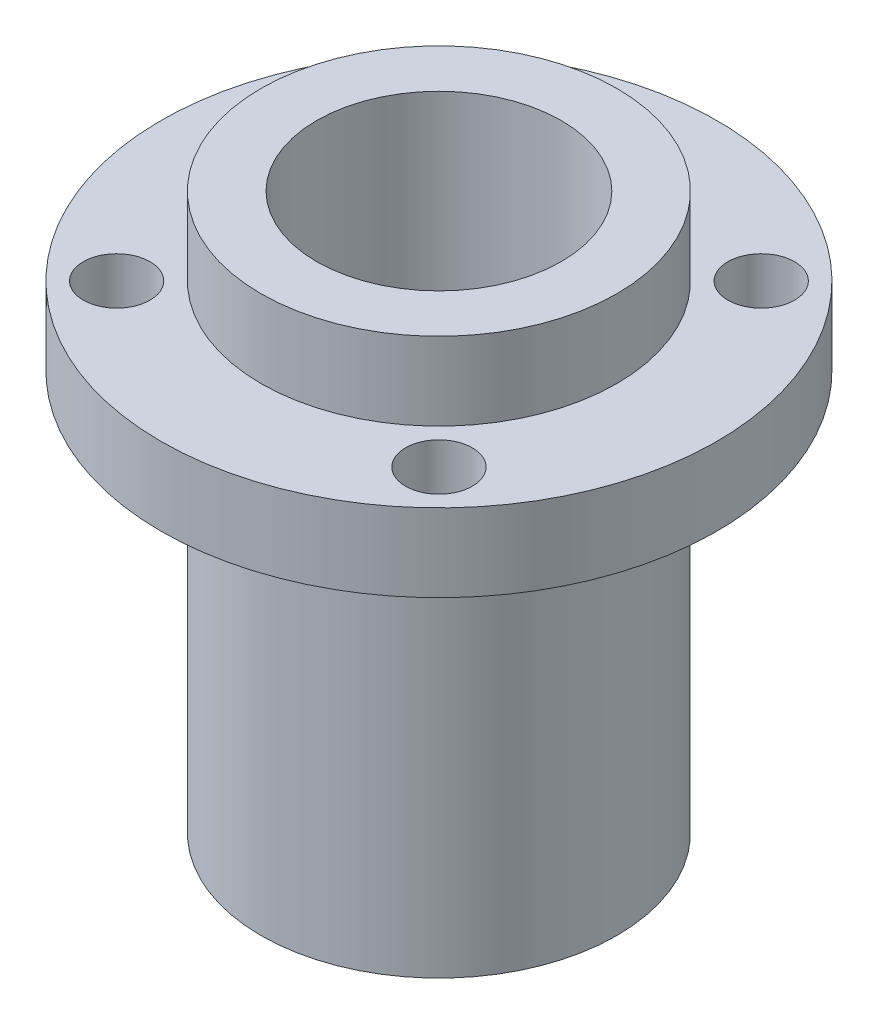
SolidWorks part; units mm, degrees
ref_plane "Front Plane" through (0, 0, 0) normal (0, 0, 1) x (1, 0, 0)
ref_plane "Top Plane" through (0, 0, 0) normal (0, 1, 0) x (1, 0, 0)
ref_plane "Right Plane" through (0, 0, 0) normal (1, 0, 0) x (0, 0, -1)
sketch "Sketch1" plane through (0, 0, 0) normal (0, 1, 0) x (1, 0, 0)
  circle A0 centre (0, 0) radius 12.5
  dimension "D1" = 25
extrude "Boss-Extrude1" add sketch "Sketch1" along normal blind 3.5
sketch "Sketch2" plane through (0, 0, 0) normal (0, 1, 0) x (1, 0, 0)
  circle A0 centre (0, 0) radius 8
  circle A1 centre (0, 0) radius 5.5
  dimension "D1" = 16
  dimension "D2" = 11
extrude "Boss-Extrude2" add sketch "Sketch2" along normal blind 3.5 from surface starting at face at (0, 3.5, 12.5)
extrude "Boss-Extrude3" add sketch "Sketch2<2>" against normal blind 18
sketch "Sketch2<2>" plane through (0, 0, 0) normal (0, 1, 0) x (1, 0, 0) same geometry as "Sketch2"
sketch "Sketch3" plane through (0, 0, 0) normal (0, 1, 0) x (1, 0, 0)
  circle A0 centre (0, 0) radius 5.5
  dimension "D1" = 11
extrude "Cut-Extrude1" cut sketch "Sketch3" along normal through all
sketch "Sketch4" plane through (0, 0, 0) normal (0, 1, 0) x (1, 0, 0)
  circle A0 centre (0, 0) radius 5.5
  circle A1 centre (0, 0) radius 2.05
  dimension "D1" = 11
  dimension "D2" = 4.1
extrude "Boss-Extrude4" add sketch "Sketch4" along normal blind 2.5 from surface starting at face at (0, -18, 5.5)
sketch "Sketch5" plane through (0, 0, 0) normal (0, 1, 0) x (1, 0, 0)
  line L0 (0, 0) -> (0, 15.5) construction
  line L1 (0, 0) -> (-10.9602, 10.9602) construction
  circle A0 centre (0, 0) radius 10.25 construction
  circle A2 centre (-7.2478, 7.2478) radius 1.5
  circle A3 centre (7.2478, 7.2478) radius 1.5
  circle A4 centre (7.2478, -7.2478) radius 1.5
  circle A5 centre (-7.2478, -7.2478) radius 1.5
  point P19 (0, 0)
  dimension "D1" = 20.5
  dimension "D3" = 3
  dimension "D2" = 45
  dimension "D4" = 4
extrude "Cut-Extrude2" cut sketch "Sketch5" along normal through all
